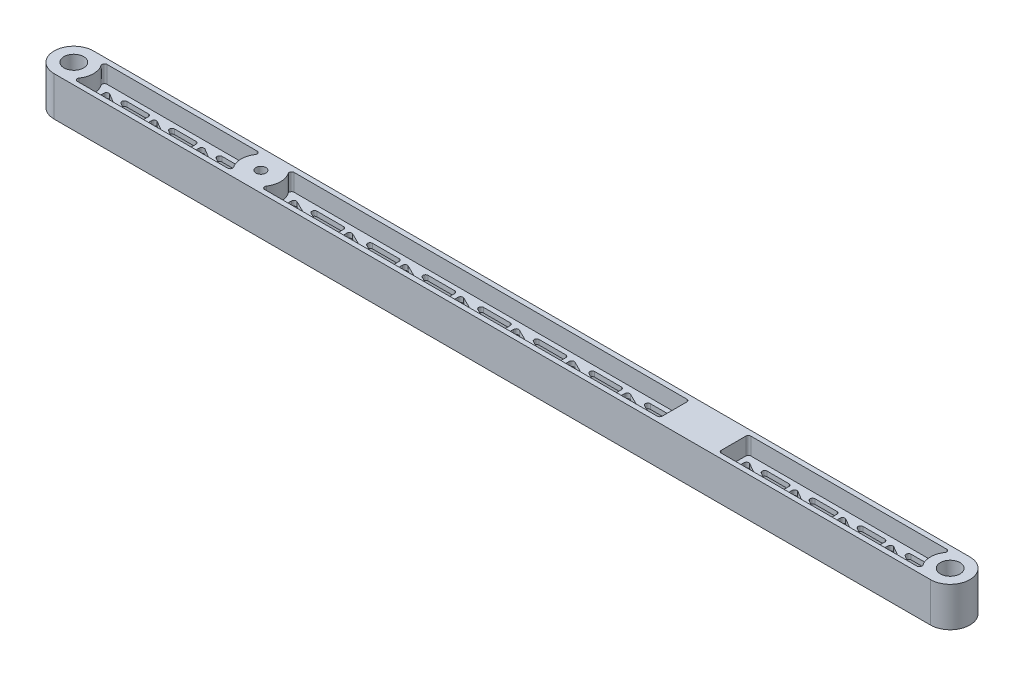
SolidWorks part; units mm, degrees
ref_plane "Front Plane" through (0, 0, 0) normal (0, 0, 1) x (1, 0, 0)
ref_plane "Top Plane" through (0, 0, 0) normal (0, 1, 0) x (1, 0, 0)
ref_plane "Right Plane" through (0, 0, 0) normal (1, 0, 0) x (0, 0, -1)
sketch "Sketch2" plane through (0, 0, 0) normal (0, 1, 0) x (1, 0, 0)
  line L0 (0, 0) -> (120.65, 0)
  line L1 (0, 0) -> (565.15, 0)
  line L2 (0, 0) -> (0, 25.4) construction
  line L3 (0, 25.4) -> (565.15, 25.4)
  line L4 (565.15, 0) -> (565.15, 25.4) construction
  line L5 (120.65, 0) -> (120.65, 25.4) construction
  circle A0 centre (120.65, 12.7) radius 12.7
  arc A1 (565.15, 25.4) -> (565.15, 0) centre (565.15, 12.7) cw
  circle A2 centre (120.65, 12.7) radius 3.175
  circle A3 centre (565.15, 12.7) radius 6.35
  arc A4 (0, 25.4) -> (0, 0) centre (0, 12.7) ccw
  circle A5 centre (0, 12.7) radius 6.35
  dimension "D4" = 6.35
  dimension "D5" = 12.7
  dimension "D6" = 12.7
  dimension "D1" = 565.15
  dimension "D2" = 25.4
  dimension "D3" = 120.65
extrude "Boss-Extrude1" add sketch "Sketch2" along normal blind 25.4 contours A0 L3 L2 L0 | A0 A2 | A1 L3 A0 L1 A3 region at (52.5215, 0, -12.7) region at (350.4658, 0, -12.7) region at (108.3092, 0, -12.7)
sketch "Sketch12" plane through (0, 0, -25.4) normal (0, 0, -1) x (-1, 0, 0)
  line L0 (-565.15, 25.4) -> (-425.45, 25.4)
  line L1 (0, 25.4) -> (-565.15, 25.4) construction
  line L2 (-387.35, 0) -> (-425.45, 0)
  line L3 (-425.45, 25.4) -> (-425.45, 0)
  line L5 (-387.35, 0) -> (-387.35, 25.4)
  line L6 (-425.45, 25.4) -> (-387.35, 25.4)
  line L7 (0, 0) -> (-565.15, 0) construction
  dimension "D1" = 139.7
  dimension "D2" = 38.1
sketch "Sketch13" plane through (0, 25.4, 0) normal (0, 1, 0) x (1, 0, 0)
  line L0 (565.15, 25.4) -> (565.15, 0) construction
  line L1 (0, 25.4) -> (0, 0) construction
  line L2 (565.15, 25.4) -> (565.15, 0) construction
  line L3 (565.15, 22.225) -> (0, 22.225)
  line L4 (0, 3.175) -> (565.15, 3.175)
  line L5 (565.15, 25.4) -> (425.45, 25.4) construction
  line L6 (0, 0) -> (565.15, 0) construction
  line L7 (12.7, 12.7) -> (15.875, 12.7) construction
  line L8 (15.875, 19.05) -> (15.875, 6.35)
  line L9 (15.875, 6.35) -> (37.189, 6.35)
  line L10 (37.189, 6.35) -> (15.875, 19.05)
  line L11 (22.0777, 19.05) -> (43.3917, 6.35)
  line L12 (43.3917, 6.35) -> (43.3917, 19.05)
  line L13 (43.3917, 19.05) -> (22.0777, 19.05)
  line L14 (46.5667, 19.05) -> (46.5667, 6.35)
  line L15 (46.5667, 6.35) -> (67.8806, 6.35)
  line L16 (67.8806, 6.35) -> (46.5667, 19.05)
  line L17 (52.7694, 19.05) -> (74.0833, 6.35)
  line L18 (74.0833, 6.35) -> (74.0833, 19.05)
  line L19 (74.0833, 19.05) -> (52.7694, 19.05)
  line L20 (43.3917, 12.7) -> (46.5667, 12.7) construction
  line L21 (77.2583, 19.05) -> (77.2583, 6.35)
  line L22 (77.2583, 6.35) -> (98.5723, 6.35)
  line L23 (98.5723, 6.35) -> (77.2583, 19.05)
  line L24 (83.461, 19.05) -> (104.775, 6.35)
  line L25 (104.775, 6.35) -> (104.775, 19.05)
  line L26 (104.775, 19.05) -> (83.461, 19.05)
  line L27 (74.0833, 12.7) -> (77.2583, 12.7) construction
  line L28 (107.95, 12.7) -> (104.775, 12.7) construction
  line L29 (133.35, 12.7) -> (136.525, 12.7) construction
  line L30 (136.525, 19.05) -> (136.525, 6.35)
  line L31 (136.525, 6.35) -> (162.0538, 6.35)
  line L32 (162.0538, 6.35) -> (136.525, 19.05)
  line L33 (143.6533, 19.05) -> (169.1821, 6.35)
  line L34 (169.1821, 6.35) -> (169.1821, 19.05)
  line L35 (169.1821, 19.05) -> (143.6533, 19.05)
  line L36 (387.35, 25.4) -> (387.35, 0)
  line L37 (425.45, 25.4) -> (387.35, 25.4) construction
  line L38 (387.35, 0) -> (425.45, 0)
  line L39 (425.45, 0) -> (425.45, 25.4)
  line L40 (387.35, 25.4) -> (425.45, 25.4) construction
  line L41 (425.45, 25.4) -> (387.35, 25.4)
  line L42 (172.3571, 19.05) -> (172.3571, 6.35)
  line L43 (172.3571, 6.35) -> (197.886, 6.35)
  line L44 (197.886, 6.35) -> (172.3571, 19.05)
  line L45 (179.4855, 19.05) -> (205.0143, 6.35)
  line L46 (205.0143, 6.35) -> (205.0143, 19.05)
  line L47 (205.0143, 19.05) -> (179.4855, 19.05)
  line L48 (169.1821, 12.7) -> (172.3571, 12.7) construction
  line L49 (208.1893, 19.05) -> (208.1893, 6.35)
  line L50 (208.1893, 6.35) -> (233.7181, 6.35)
  line L51 (233.7181, 6.35) -> (208.1893, 19.05)
  line L52 (215.3176, 19.05) -> (240.8464, 6.35)
  line L53 (240.8464, 6.35) -> (240.8464, 19.05)
  line L54 (240.8464, 19.05) -> (215.3176, 19.05)
  line L55 (205.0143, 12.7) -> (208.1893, 12.7) construction
  line L56 (244.0214, 19.05) -> (244.0214, 6.35)
  line L57 (244.0214, 6.35) -> (269.5502, 6.35)
  line L58 (269.5502, 6.35) -> (244.0214, 19.05)
  line L59 (251.1498, 19.05) -> (276.6786, 6.35)
  line L60 (276.6786, 6.35) -> (276.6786, 19.05)
  line L61 (276.6786, 19.05) -> (251.1498, 19.05)
  line L62 (240.8464, 12.7) -> (244.0214, 12.7) construction
  line L63 (279.8536, 19.05) -> (279.8536, 6.35)
  line L64 (279.8536, 6.35) -> (305.3824, 6.35)
  line L65 (305.3824, 6.35) -> (279.8536, 19.05)
  line L66 (286.9819, 19.05) -> (312.5107, 6.35)
  line L67 (312.5107, 6.35) -> (312.5107, 19.05)
  line L68 (312.5107, 19.05) -> (286.9819, 19.05)
  line L69 (276.6786, 12.7) -> (279.8536, 12.7) construction
  line L70 (315.6857, 19.05) -> (315.6857, 6.35)
  line L71 (315.6857, 6.35) -> (341.2145, 6.35)
  line L72 (341.2145, 6.35) -> (315.6857, 19.05)
  line L73 (322.814, 19.05) -> (348.3429, 6.35)
  line L74 (348.3429, 6.35) -> (348.3429, 19.05)
  line L75 (348.3429, 19.05) -> (322.814, 19.05)
  line L76 (312.5107, 12.7) -> (315.6857, 12.7) construction
  line L77 (351.5179, 19.05) -> (351.5179, 6.35)
  line L78 (351.5179, 6.35) -> (377.0467, 6.35)
  line L79 (377.0467, 6.35) -> (351.5179, 19.05)
  line L80 (358.6462, 19.05) -> (384.175, 6.35)
  line L81 (384.175, 6.35) -> (384.175, 19.05)
  line L82 (384.175, 19.05) -> (358.6462, 19.05)
  line L83 (348.3429, 12.7) -> (351.5179, 12.7) construction
  line L84 (425.45, 12.7) -> (428.625, 12.7) construction
  line L85 (428.625, 19.05) -> (428.625, 6.35)
  line L86 (428.625, 6.35) -> (450.1567, 6.35)
  line L87 (450.1567, 6.35) -> (428.625, 19.05)
  line L88 (434.8745, 19.05) -> (456.4062, 6.35)
  line L89 (456.4062, 6.35) -> (456.4062, 19.05)
  line L90 (456.4062, 19.05) -> (434.8745, 19.05)
  line L91 (459.5812, 19.05) -> (459.5812, 6.35)
  line L92 (459.5812, 6.35) -> (481.113, 6.35)
  line L93 (481.113, 6.35) -> (459.5812, 19.05)
  line L94 (465.8308, 19.05) -> (487.3625, 6.35)
  line L95 (487.3625, 6.35) -> (487.3625, 19.05)
  line L96 (487.3625, 19.05) -> (465.8308, 19.05)
  line L97 (456.4062, 12.7) -> (459.5812, 12.7) construction
  line L98 (490.5375, 19.05) -> (490.5375, 6.35)
  line L99 (490.5375, 6.35) -> (512.0692, 6.35)
  line L100 (512.0692, 6.35) -> (490.5375, 19.05)
  line L101 (496.787, 19.05) -> (518.3187, 6.35)
  line L102 (518.3187, 6.35) -> (518.3187, 19.05)
  line L103 (518.3187, 19.05) -> (496.787, 19.05)
  line L104 (487.3625, 12.7) -> (490.5375, 12.7) construction
  line L105 (521.4937, 19.05) -> (521.4937, 6.35)
  line L106 (521.4937, 6.35) -> (543.0255, 6.35)
  line L107 (543.0255, 6.35) -> (521.4937, 19.05)
  line L108 (527.7433, 19.05) -> (549.275, 6.35)
  line L109 (549.275, 6.35) -> (549.275, 19.05)
  line L110 (549.275, 19.05) -> (527.7433, 19.05)
  line L111 (518.3187, 12.7) -> (521.4937, 12.7) construction
  line L113 (565.15, 12.7) -> (552.45, 12.7) construction
  line L114 (552.45, 12.7) -> (552.45, 25.4) construction
  line L115 (552.45, 25.4) -> (552.45, 3.175) construction
  circle A0 centre (565.15, 12.7) radius 12.7
  circle A1 centre (120.65, 12.7) radius 12.7
  circle A2 centre (0, 12.7) radius 12.7
  dimension "D1" = 25.4
  dimension "D9" = 3.175
  dimension "D2" = 3.175
  dimension "D3" = 3.175
  dimension "D4" = 3.175
  dimension "D5" = 3.175
  dimension "D6" = 3.175
  dimension "D7" = 3.175
  dimension "D10" = 3.175
  dimension "D11" = 3.175
  dimension "D12" = 3.175
  dimension "D13" = 3.175
  dimension "D14" = 3.175
  dimension "D15" = 139.7
  dimension "D16" = 38.1
  dimension "D17" = 7
  dimension "D18" = 3.175
  dimension "D19" = 3.175
  dimension "D20" = 3.175
  dimension "D21" = 3.175
  dimension "D22" = 3.175
  dimension "D23" = 3.175
  dimension "D25" = 3.175
  dimension "D26" = 3.175
  dimension "D8" = 3
  dimension "D24" = 4
extrude "Cut-Extrude2" cut sketch "Sketch13" against normal through all contours L109 L110 L108 | L106 L107 L105 | L102 L103 L101 | L99 L100 L98 | L92 L93 L91 | L89 L90 L88 | L86 L87 L85 | L78 L79 L77 | L81 L82 L80 | L74 L75 L73 | L71 L72 L70 | L67 L68 L66 | L64 L65 L63 | L60 L61 L59 | L57 L58 L56 | L53 L54 L52 | L50 L51 L49 | L46 L47 L45 | L43 L44 L42 | L34 L35 L33 | L31 L32 L30 | L25 L26 L24 | L22 L23 L21 | L18 L19 L17 | L15 L16 L14 | L12 L13 L11 | L9 L10 L8 | L96 L94 L95 region at (22.9797, 25.4, -10.5833) region at (36.287, 25.4, -14.8167) region at (53.6713, 25.4, -10.5833) region at (66.9787, 25.4, -14.8167) region at (84.363, 25.4, -10.5833) region at (97.6703, 25.4, -14.8167) region at (145.0346, 25.4, -10.5833) region at (160.6725, 25.4, -14.8167) region at (180.8667, 25.4, -10.5833) region at (196.5047, 25.4, -14.8167) region at (216.6989, 25.4, -10.5833) region at (232.3368, 25.4, -14.8167) region at (252.531, 25.4, -10.5833) region at (268.169, 25.4, -14.8167) region at (288.3632, 25.4, -10.5833) region at (304.0011, 25.4, -14.8167) region at (324.1953, 25.4, -10.5833) region at (339.8333, 25.4, -14.8167) region at (360.0275, 25.4, -10.5833) region at (375.6654, 25.4, -14.8167) region at (435.8022, 25.4, -10.5833) region at (449.229, 25.4, -14.8167) region at (466.7585, 25.4, -10.5833) region at (497.7147, 25.4, -10.5833) region at (511.1415, 25.4, -14.8167) region at (528.671, 25.4, -10.5833) region at (542.0978, 25.4, -14.8167)
extrude "Cut-Extrude3" cut sketch "Sketch13<4>" against normal blind 11.1125 contours A2 L4 A1 L3 L10 L9 L8 L13 L12 L11 L16 L15 L14 L19 L18 L17 L23 L22 L21 L26 L25 L24 | A1 L4 L36 L3 L32 L31 L30 L35 L34 L33 L44 L43 L42 L47 L46 L45 L51 L50 L49 L54 L53 L52 L58 L57 L56 L61 L60 L59 L65 L64 L63 L68 L67 L66 L72 L71 L70 L75 L74 | A0 L3 L39 L4 L87 L86 L85 L90 L89 L88 L93 L92 L91 L96 L95 L94 L100 L99 L98 L103 L102 L101 L107 L106 L105 L110 L109 L108 region at (490.155, 25.4, -12.7) region at (259.1074, 25.4, -12.7) region at (60.325, 25.4, -12.7)
sketch "Sketch13<4>" plane through (0, 25.4, 0) normal (0, 1, 0) x (1, 0, 0) same geometry as "Sketch13"
ref_plane "Plane1" through (0, 12.7, 0) normal (0, -1, 0) x (-1, 0, 0)
mirror "Mirror1" about plane through (0, 12.7, 0) normal (0, -1, 0) of "Cut-Extrude3"
fillet "Fillet1" radius 1.5875 108 edges at (104.775, 12.7, -19.05) (83.461, 12.7, -19.05) (98.5723, 12.7, -6.35) (77.2583, 12.7, -6.35) (77.2583, 12.7, -19.05) (74.0833, 12.7, -19.05) (74.0833, 12.7, -6.35) (52.7694, 12.7, -19.05) (67.8806, 12.7, -6.35) (46.5667, 12.7, -6.35) (46.5667, 12.7, -19.05) (43.3917, 12.7, -19.05) (43.3917, 12.7, -6.35) (22.0777, 12.7, -19.05) (37.189, 12.7, -6.35) (15.875, 12.7, -6.35) (15.875, 12.7, -19.05) (104.775, 12.7, -6.35) (384.175, 12.7, -19.05) (358.6462, 12.7, -19.05) (377.0467, 12.7, -6.35) (351.5179, 12.7, -6.35) (351.5179, 12.7, -19.05) (348.3429, 12.7, -19.05) (348.3429, 12.7, -6.35) (322.814, 12.7, -19.05) (341.2145, 12.7, -6.35) (315.6857, 12.7, -6.35) (315.6857, 12.7, -19.05) (312.5107, 12.7, -19.05) (312.5107, 12.7, -6.35) (286.9819, 12.7, -19.05) (305.3824, 12.7, -6.35) (279.8536, 12.7, -6.35) (279.8536, 12.7, -19.05) (276.6786, 12.7, -19.05) (276.6786, 12.7, -6.35) (251.1498, 12.7, -19.05) (269.5502, 12.7, -6.35) (244.0214, 12.7, -6.35) (244.0214, 12.7, -19.05) (240.8464, 12.7, -19.05) (240.8464, 12.7, -6.35) (215.3176, 12.7, -19.05) (233.7181, 12.7, -6.35) (208.1893, 12.7, -6.35) (208.1893, 12.7, -19.05) (205.0143, 12.7, -19.05) (205.0143, 12.7, -6.35) (179.4855, 12.7, -19.05) (197.886, 12.7, -6.35) (172.3571, 12.7, -6.35) (172.3571, 12.7, -19.05) (169.1821, 12.7, -19.05) (169.1821, 12.7, -6.35) (143.6533, 12.7, -19.05) (162.0538, 12.7, -6.35) (136.525, 12.7, -6.35) (136.525, 12.7, -19.05) (384.175, 12.7, -6.35) (112.2497, 5.5562, -22.225) (112.2497, 5.5562, -3.175) (8.4003, 5.5562, -3.175) (8.4003, 5.5562, -22.225) (387.35, 5.5562, -22.225) (129.0503, 5.5562, -3.175) (129.0503, 5.5562, -22.225) (387.35, 5.5562, -3.175) (425.45, 19.8438, -22.225) (425.45, 19.8438, -3.175) (556.7497, 19.8438, -3.175) (112.2497, 19.8438, -3.175) (112.2497, 19.8438, -22.225) (8.4003, 19.8438, -22.225) (8.4003, 19.8438, -3.175) (387.35, 19.8438, -3.175) (387.35, 19.8438, -22.225) (129.0503, 19.8438, -22.225) (129.0503, 19.8438, -3.175) (556.7497, 19.8438, -22.225) (549.275, 12.7, -6.35) (527.7433, 12.7, -19.05) (543.0255, 12.7, -6.35) (521.4937, 12.7, -6.35) (521.4937, 12.7, -19.05) (518.3187, 12.7, -19.05) (518.3187, 12.7, -6.35) (496.787, 12.7, -19.05) (512.0692, 12.7, -6.35) (490.5375, 12.7, -6.35) (490.5375, 12.7, -19.05) (487.3625, 12.7, -19.05) (487.3625, 12.7, -6.35) (465.8308, 12.7, -19.05) (481.113, 12.7, -6.35) (459.5812, 12.7, -6.35) (459.5812, 12.7, -19.05) (456.4062, 12.7, -19.05) (456.4062, 12.7, -6.35) (434.8745, 12.7, -19.05) (450.1567, 12.7, -6.35) (428.625, 12.7, -6.35) (428.625, 12.7, -19.05) (549.275, 12.7, -19.05) (556.7497, 5.5562, -22.225) (425.45, 5.5562, -22.225) (425.45, 5.5562, -3.175) (556.7497, 5.5562, -3.175)
